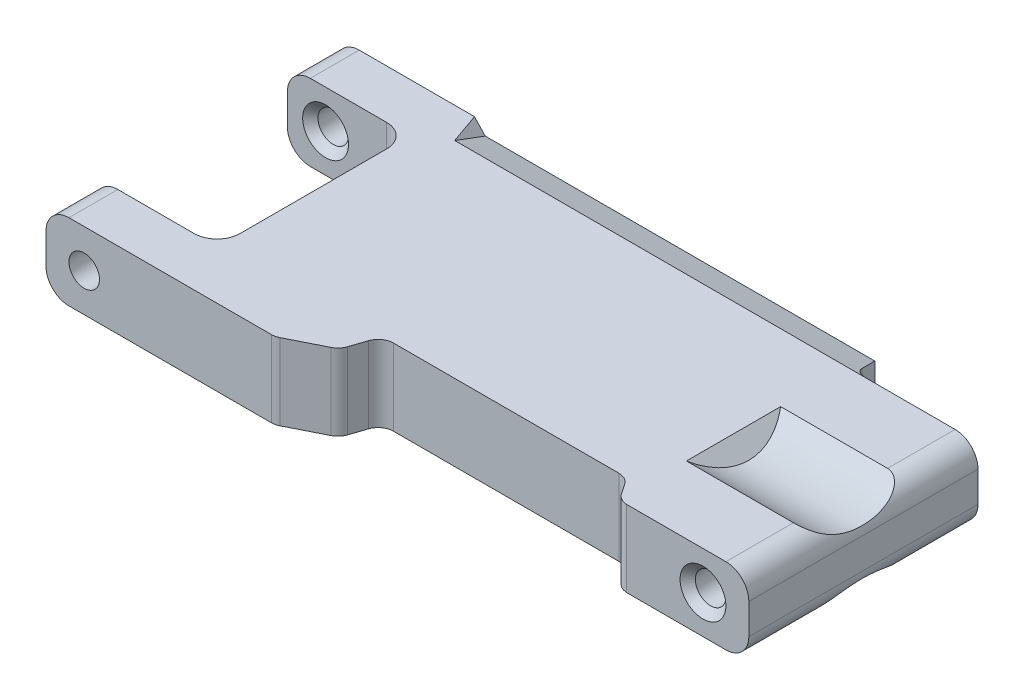
SolidWorks part; units mm, degrees
ref_plane "Front Plane" through (0, 0, 0) normal (0, 0, 1) x (1, 0, 0)
ref_plane "Top Plane" through (0, 0, 0) normal (0, 1, 0) x (1, 0, 0)
ref_plane "Right Plane" through (0, 0, 0) normal (1, 0, 0) x (0, 0, -1)
ref_plane "Plane1" through (0, 0, 0) normal (0, 1, 0) x (1, 0, 0)
sketch "Sketch1" plane through (0, 0, 0) normal (0, 1, 0) x (1, 0, 0)
  line L0 (-35.25, 0) -> (-35.25, -6.4)
  line L1 (-35.25, -6.4) -> (-22.25, -6.4)
  line L2 (-19.25, -9.4) -> (-19.25, -28.6)
  line L3 (-22.25, -31.6) -> (-35.25, -31.6)
  line L4 (-35.25, -31.6) -> (-35.25, -38)
  line L5 (-35.25, -38) -> (-5.75, -38)
  line L6 (-4.8528, -37.7875) -> (-0.3841, -35.5446)
  line L7 (0.6161, -34.3896) -> (1.3007, -32.3358)
  line L8 (3.198, -30.9683) -> (32.698, -30.9683)
  line L9 (34.3636, -31.8611) -> (35.194, -33.1102)
  line L10 (36.75, -34) -> (52.75, -34)
  line L11 (52.75, -34) -> (52.75, -4)
  line L12 (52.75, -4) -> (38.136, -4)
  line L13 (36.2633, -2.7022) -> (35.25, 0)
  line L14 (35.25, 0) -> (-35.25, 0)
  arc A0 (-22.25, -6.4) -> (-19.25, -9.4) centre (-22.25, -9.4) cw
  arc A1 (-19.25, -28.6) -> (-22.25, -31.6) centre (-22.25, -28.6) cw
  arc A2 (-5.75, -38) -> (-4.8528, -37.7875) centre (-5.75, -36) ccw
  arc A3 (-0.3841, -35.5446) -> (0.6161, -34.3896) centre (-1.2813, -33.7571) ccw
  arc A4 (1.3007, -32.3358) -> (3.198, -30.9683) centre (3.198, -32.9683) cw
  arc A5 (32.698, -30.9683) -> (34.3636, -31.8611) centre (32.698, -32.9683) cw
  arc A6 (35.194, -33.1102) -> (36.75, -34) centre (36.8596, -32.003) ccw
  arc A7 (38.136, -4) -> (36.2633, -2.7022) centre (38.136, -2) cw
  dimension "D3" = 2
  dimension "D9" = 3
  dimension "D11" = 2
  dimension "D13" = 2
  dimension "D15" = 2
  dimension "D17" = 1.5
  dimension "D1" = 30
  dimension "D2" = 14.614
  dimension "D4" = 2.886
  dimension "D5" = 70.5
  dimension "D6" = 6.4
  dimension "D7" = 13
  dimension "D8" = 19.2
  dimension "D10" = 29.5
  dimension "D12" = 5
  dimension "D14" = 2.1648
  dimension "D16" = 29.5
  dimension "D18" = 16
  dimension "D19" = 69.444
  dimension "D20" = 153.348
  dimension "D21" = 135.087
extrude "Boss-Extrude1" add sketch "Sketch1" along normal blind 10
fillet "Fillet1" radius 3 6 edges at (-35.25, 10, 3.2) (-35.25, 10, 34.8) (-35.25, 0, 34.8) (-35.25, 0, 3.2) (52.75, 0, 19) (52.75, 10, 19)
ref_plane "Plane2" through (38.136, 0, 0) normal (1, 0, 0) x (0, 0, -1)
sketch "Sketch2" plane through (38.136, 0, 0) normal (1, 0, 0) x (0, 0, -1)
  line L0 (-4, 10) -> (0, 10)
  line L1 (0, 10) -> (0, 8.5)
  line L2 (0, 10) -> (0, 0) construction
  line L3 (0, 8.5) -> (-4, 10)
  dimension "D1" = 1.5
extrude "Cut-Extrude1" cut sketch "Sketch2" against normal blind 55.386
chamfer "Chamfer1" distance 1.5 angle 45 1 edges at (-17.25, 9.25, 2)
ref_plane "Plane4" through (0, 5, 0) normal (0, 1, 0) x (1, 0, 0)
mirror "Mirror3" about plane through (0, 5, 0) normal (0, 1, 0) of "Cut-Extrude1", "Chamfer1"
hole_wizard "CSK for M4 SFHCS1" positions "Sketch3" profile "Sketch4" countersink size "M4" standard "ANSI Metric" end condition through all
sketch "Sketch3" plane through (0, 0, 6.4) normal (0, 0, 1) x (1, 0, 0)
  line L0 (-30.25, 10) -> (-30.25, 5) construction
  line L1 (-32.25, 10) -> (-22.25, 10) construction
  line L2 (-30.25, 5) -> (-30.25, 0) construction
  line L3 (-32.25, 0) -> (-22.25, 0) construction
  line L5 (-30.25, 5) -> (-35.25, 5) construction
  line L6 (-35.25, 7) -> (-35.25, 3) construction
  point P0 (-30.25, 5)
  dimension "D1" = 5
sketch "Sketch4" plane through (-30.25, 5, 6.4) normal (1, 0, 0) x (0, -1, 0)
  line L0 (0, 0) -> (0, 6.4)
  line L1 (0, 6.4) -> (2, 6.4)
  line L2 (2, 6.4) -> (2, 1)
  line L3 (2, 1) -> (3, 0)
  line L5 (3, 0) -> (0, 0)
  line L6 (-2, 1) -> (-3, 0) construction
  line L11 (0, -6.35) -> (0, 107.95) construction
  dimension "Thru Hole Dia." = 4
  dimension "Thru Hole Depth" = 6.4
  dimension "Near C'Sink Dia." = 6
  dimension "Near C'Sink Angle" = 90
ref_plane "Plane3" through (0, 0, 19) normal (0, 0, 1) x (1, 0, 0)
mirror "Mirror1" about plane through (0, 0, 19) normal (0, 0, 1) of "CSK for M4 SFHCS1"
hole_wizard "CSK for M4 SFHCS2" positions "Sketch5" profile "Sketch6" countersink size "M4" standard "ANSI Metric" end condition through all
sketch "Sketch5" plane through (0, 0, 34) normal (0, 0, 1) x (1, 0, 0)
  line L0 (46.75, 5) -> (46.75, 10) construction
  line L1 (36.75, 10) -> (49.75, 10) construction
  line L3 (46.75, 5) -> (46.75, 0) construction
  line L4 (36.75, 0) -> (49.75, 0) construction
  line L6 (46.75, 5) -> (52.75, 5) construction
  line L7 (52.75, 7) -> (52.75, 3) construction
  point P0 (46.75, 5)
  dimension "D1" = 6
sketch "Sketch6" plane through (46.75, 5, 34) normal (1, 0, 0) x (0, -1, 0)
  line L0 (0, 0) -> (0, 34)
  line L1 (0, 34) -> (2, 34)
  line L2 (2, 34) -> (2, 1)
  line L3 (2, 1) -> (3, 0)
  line L5 (3, 0) -> (0, 0)
  line L6 (-2, 1) -> (-3, 0) construction
  line L11 (0, -6.35) -> (0, 107.95) construction
  dimension "Thru Hole Dia." = 4
  dimension "Thru Hole Depth" = 34
  dimension "Near C'Sink Dia." = 6
  dimension "Near C'Sink Angle" = 90
mirror "Mirror2" about plane through (0, 0, 19) normal (0, 0, 1) of "CSK for M4 SFHCS2"
sketch "Sketch7" plane through (0, 0, 0) normal (0, 0, -1) x (-1, 0, 0)
  line L0 (-31.25, 5) -> (-35.25, 5) construction
  line L1 (-35.25, 8.5) -> (-35.25, 1.5) construction
  circle A0 centre (-31.25, 5) radius 1.5
  circle A1 centre (-23.75, 5) radius 1.5
  circle A2 centre (-16.25, 5) radius 1.5
  circle A3 centre (-8.75, 5) radius 1.5
  circle A4 centre (-1.25, 5) radius 1.5
  circle A5 centre (6.25, 5) radius 1.5
  circle A6 centre (13.75, 5) radius 1.5
  dimension "D1" = 3
  dimension "D2" = 4
  dimension "D4" = 7.5
  dimension "D3" = 7
extrude "Cut-Extrude2" cut sketch "Sketch7" against normal blind 24
sketch "Sketch8" plane through (52.75, 0, 0) normal (1, 0, 0) x (0, 0, -1)
  line L0 (-19, 18.5) -> (-19, -8.5) construction
  line L1 (-19, 7) -> (-19, 3) construction
  line L2 (-4, 7) -> (-34, 7) construction
  line L3 (-34, 3) -> (-4, 3) construction
  circle A0 centre (-19, 18.5) radius 10.5
  circle A1 centre (-19, -8.5) radius 10.5
  point P3 (-19, 5)
  point P10 (-19, 5)
  dimension "D2" = 21
  dimension "D1" = 27
extrude "Cut-Extrude3" cut sketch "Sketch8" against normal blind 15
chamfer "Chamfer2" distance 2 angle 45 2 edges at (37.75, 0, 19) (37.75, 10, 19)
